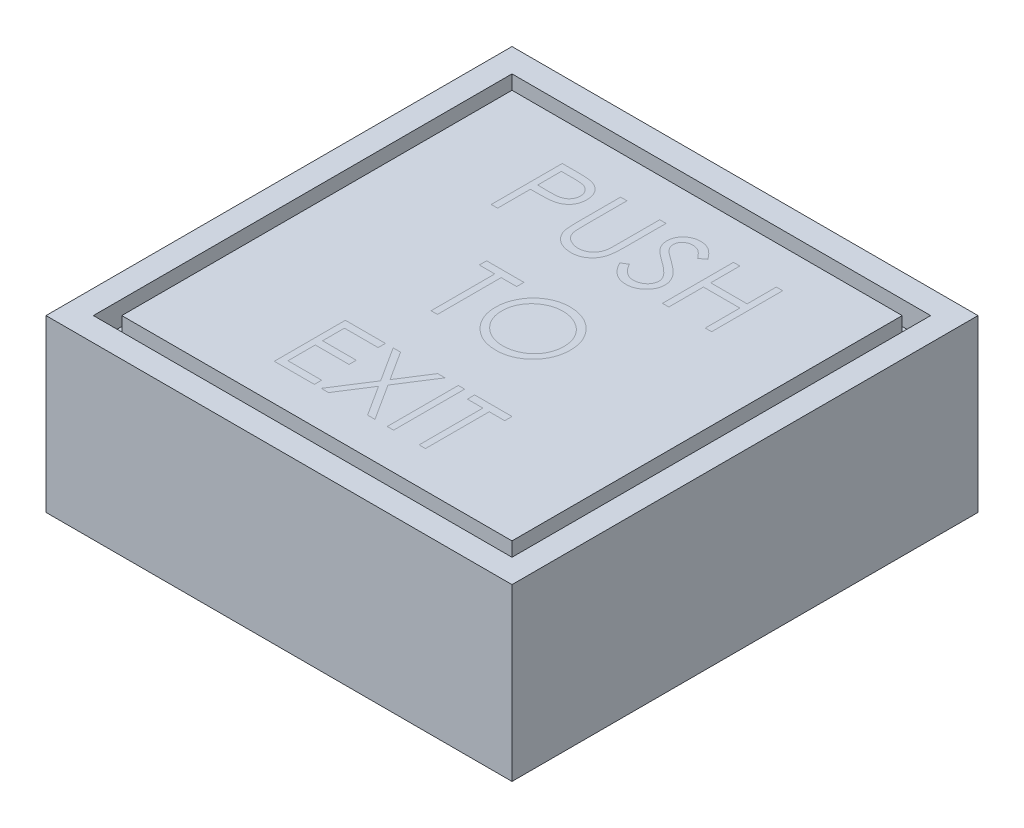
SolidWorks part; units mm, degrees
material "Stainless Steel (ferritic)"
ref_plane "Front Plane" through (0, 0, 0) normal (0, 0, 1) x (1, 0, 0)
ref_plane "Back of Button Plane" through (0, 0, 0) normal (0, 1, 0) x (1, 0, 0)
ref_plane "Right Plane" through (0, 0, 0) normal (1, 0, 0) x (0, 0, -1)
sketch "Sketch1" plane through (0, 0, 0) normal (0, 1, 0) x (1, 0, 0)
  line L1 (0, 0) -> (124.968, 0)
  line L2 (0, 0) -> (0, 124.968)
  line L3 (0, 124.968) -> (124.968, 124.968)
  line L4 (124.968, 0) -> (124.968, 124.968)
  dimension "D1" = 124.968
  dimension "D2" = 124.968
extrude "Boss-Extrude1" add sketch "Sketch1" along normal blind 45.72
sketch "Sketch4" plane through (0, 45.72, 0) normal (0, 1, 0) x (1, 0, 0)
  line L8 (6.35, 118.618) -> (6.35, 6.35)
  line L9 (6.35, 6.35) -> (118.618, 6.35)
  line L10 (118.618, 6.35) -> (118.618, 118.618)
  line L11 (118.618, 118.618) -> (6.35, 118.618)
  line L12 (6.35, 118.618) -> (6.35, 6.35)
  line L13 (6.35, 6.35) -> (118.618, 6.35)
  line L14 (118.618, 6.35) -> (118.618, 118.618)
  line L15 (118.618, 118.618) -> (6.35, 118.618)
  dimension "D1" = 6.35
extrude "Cut-Extrude1" cut sketch "Sketch4" against normal blind 6.35
sketch "Sketch6" plane through (0, 39.37, 0) normal (0, 1, 0) x (1, 0, 0)
  line L8 (114.808, 10.16) -> (114.808, 114.808)
  line L9 (10.16, 10.16) -> (114.808, 10.16)
  line L10 (10.16, 114.808) -> (10.16, 10.16)
  line L11 (114.808, 114.808) -> (10.16, 114.808)
  line L12 (114.808, 10.16) -> (114.808, 114.808)
  line L13 (10.16, 10.16) -> (114.808, 10.16)
  line L14 (10.16, 114.808) -> (10.16, 10.16)
  line L15 (114.808, 114.808) -> (10.16, 114.808)
  dimension "D1" = 3.81
extrude "Boss-Extrude2" add sketch "Sketch6" along normal blind 6.35
sketch "Sketch11" plane through (0, 45.72, 0) normal (0, 1, 0) x (1, 0, 0)
  text T0 "PUSH \r\n  TO\r\n EXIT" font "Century Gothic" height in points 72
wrap "Wrap1" sketch "Sketch11" wrap type scribe source sketch "Sketch11" face at (62.484, 45.72, -62.484)
